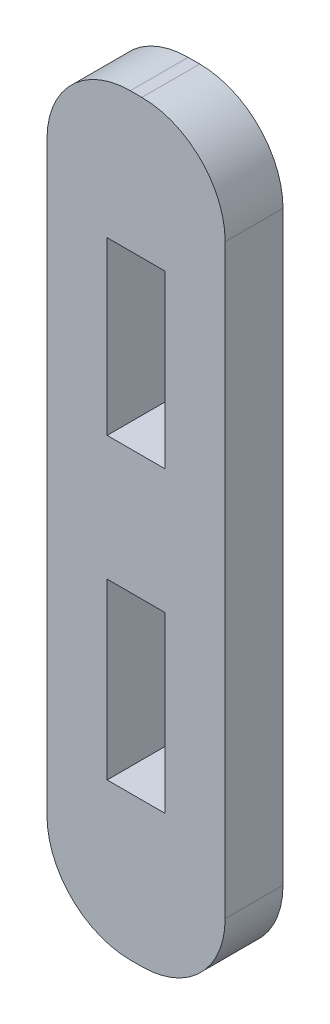
SolidWorks part; units mm, degrees
ref_plane "Front Plane" through (0, 0, 0) normal (0, 0, 1) x (1, 0, 0)
ref_plane "Top Plane" through (0, 0, 0) normal (0, 1, 0) x (1, 0, 0)
ref_plane "Right Plane" through (0, 0, 0) normal (1, 0, 0) x (0, 0, -1)
sketch "Sketch1" plane through (0, 0, 0) normal (0, 0, 1) x (1, 0, 0)
  line L0 (3.2385, 19.0082) -> (1.651, 19.0082) construction
  line L1 (0, 0) -> (4.8895, 0)
  line L2 (0, 0) -> (0, 20.6592)
  line L3 (0, 20.6592) -> (4.8895, 20.6592)
  line L4 (4.8895, 0) -> (4.8895, 20.6592)
  line L7 (3.2385, 16.8492) -> (3.2385, 19.0082) construction
  dimension "D1" = 1.651
  dimension "D2" = 1.651
extrude "Boss-Extrude1" add sketch "Sketch1" along normal blind 1.5875
sketch "Sketch2" plane through (0, 0, 0) normal (0, 0, -1) x (-1, 0, 0)
  line L1 (-3.2385, 14.3092) -> (-3.2385, 12.1502)
  line L2 (-3.2385, 12.1502) -> (-1.651, 12.1502)
  line L3 (-1.651, 12.1502) -> (-1.651, 14.3092)
  line L4 (-1.651, 15.7927) -> (-1.651, 18.6766) construction
  line L6 (-1.651, 16.8492) -> (-1.651, 19.0082) construction
  line L7 (-3.2385, 15.7927) -> (-3.2385, 18.6766) construction
  line L8 (-1.651, 5.2318) -> (-1.651, 6.4235) construction
  line L9 (-3.2385, 5.2318) -> (-3.2385, 4.8665) construction
  line L10 (-3.2385, 16.8492) -> (-1.651, 16.8492) construction
  line L11 (-3.2385, 6.4235) -> (-3.2385, 5.2318) construction
  line L12 (-1.651, 4.8665) -> (-1.651, 5.2318) construction
  line L13 (-1.651, 5.2318) -> (-1.651, 6.4235)
  line L14 (-1.651, 15.4654) -> (-1.651, 15.7927) construction
  line L15 (-1.651, 14.3092) -> (-1.651, 15.4654) construction
  line L16 (-3.2385, 16.8492) -> (-1.651, 16.8492)
  line L17 (-3.2385, 15.7927) -> (-3.2385, 15.4654) construction
  line L18 (-3.2385, 15.4654) -> (-3.2385, 14.3092) construction
  line L19 (-1.651, 15.7927) -> (-1.651, 16.8492)
  line L20 (-3.2385, 5.2318) -> (-3.2385, 4.8665)
  line L21 (-3.2385, 6.4235) -> (-3.2385, 5.2318)
  line L22 (-3.2385, 3.9617) -> (-1.651, 3.9617) construction
  line L25 (-3.2385, 15.7927) -> (-3.2385, 16.8492)
  line L26 (-1.651, 15.4654) -> (-1.651, 15.7927)
  line L27 (-1.651, 14.3092) -> (-1.651, 15.4654)
  line L28 (-3.2385, 15.7927) -> (-3.2385, 15.4654)
  line L29 (-3.2385, 3.9617) -> (-1.651, 3.9617)
  line L30 (-1.651, 4.8665) -> (-1.651, 5.2318)
  line L31 (-1.651, 1.9826) -> (-1.651, 4.8665) construction
  line L32 (-3.2385, 15.4654) -> (-3.2385, 14.3092)
  line L33 (-3.2385, 6.4235) -> (-3.2385, 8.7342)
  line L34 (-3.2385, 8.7342) -> (-1.651, 8.7342)
  line L35 (-1.651, 8.7342) -> (-1.651, 6.4235)
  line L36 (-1.651, 3.9617) -> (-1.651, 1.651) construction
  line L37 (-0.8554, 16.8492) -> (-0.8554, 19.0082) construction
  line L38 (-3.2385, 1.9826) -> (-3.2385, 4.8665) construction
  line L39 (-1.651, 3.9617) -> (-1.651, 4.8665)
  line L40 (-3.2385, 3.9617) -> (-3.2385, 4.8665)
  line L41 (-0.8554, 1.651) -> (-0.8554, 3.9617) construction
extrude "Cut-Extrude1" cut sketch "Sketch2" against normal through all
fillet "Fillet1" radius 2.286 4 edges at (0, 0, 0.7937) (4.8895, 0, 0.7937) (4.8895, 20.6592, 0.7937) (0, 20.6592, 0.7937)
